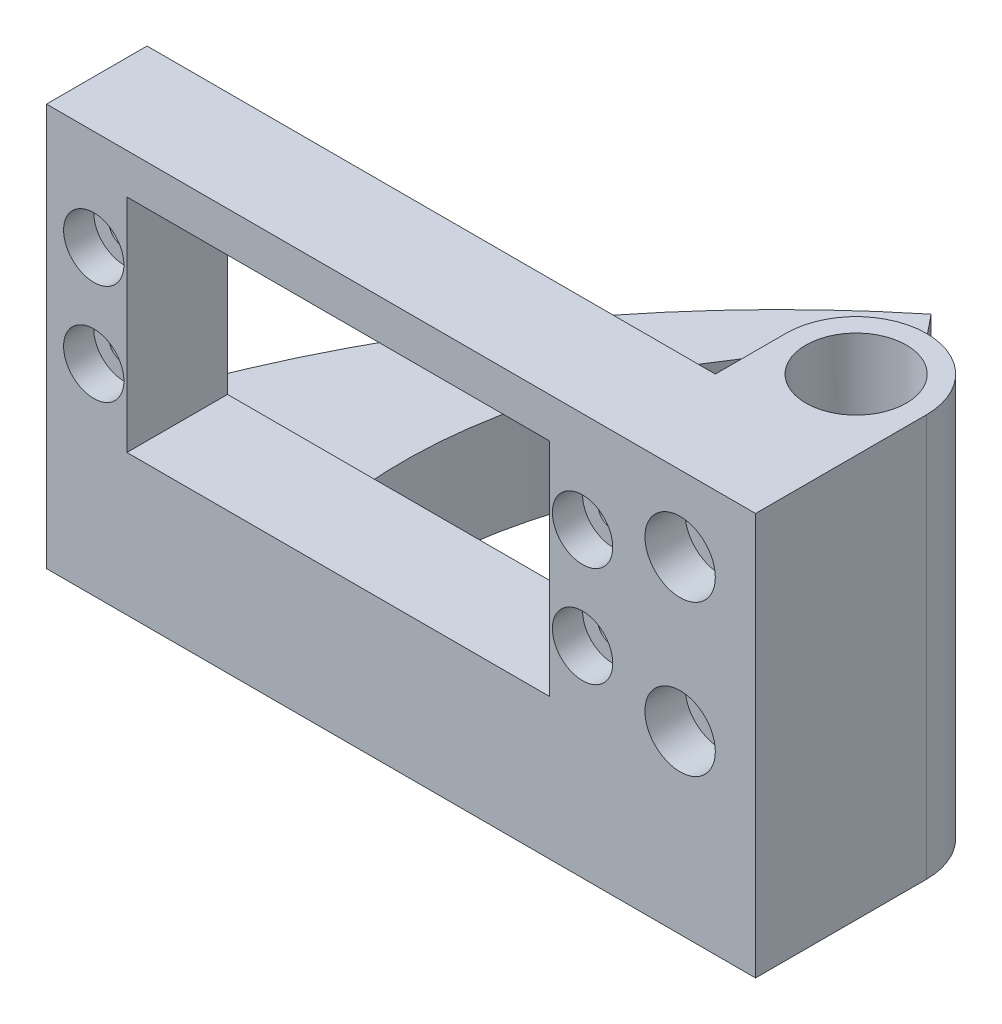
SolidWorks part; units mm, degrees
ref_plane "Front Plane" through (0, 0, 0) normal (0, 0, 1) x (1, 0, 0)
ref_plane "Top Plane" through (0, 0, 0) normal (0, 1, 0) x (1, 0, 0)
ref_plane "Right Plane" through (0, 0, 0) normal (1, 0, 0) x (0, 0, -1)
ref_axis "X" through (-88.99, 0, 0) along (1, 0, 0)
ref_axis "Y" through (0, 55, 0) along (0, -1, 0)
ref_axis "Z" through (0, 0, -88.99) along (0, 0, 1)
sketch "Sketch1" plane through (0, 0, 0) normal (0, 0, 1) x (1, 0, 0)
  line L0 (34, -7.5) -> (34, 7.5) construction
  line L1 (0, 0) -> (34, 0) construction
  line L2 (24.3, 5) -> (24.3, -5) construction
  line L3 (-21, 11) -> (21, 11)
  line L4 (-21, 11) -> (-21, -11)
  line L5 (-21, -11) -> (21, -11)
  line L6 (21, 11) -> (21, -11)
  line L7 (-21, 11) -> (21, -11) construction
  line L8 (-21, -11) -> (21, 11) construction
  line L9 (0, 0) -> (0, 11) construction
  line L10 (34, -15) -> (-29, -15)
  line L11 (-29, -15) -> (-29, 15)
  line L12 (-29, 15) -> (34, 15)
  line L13 (41.5, 7.5) -> (41.5, -7.5)
  line L14 (34, 0) -> (41.5, 0) construction
  line L15 (34, -15) -> (41.5, -15)
  line L16 (41.5, -15) -> (41.5, -7.5)
  line L17 (34, 15) -> (41.5, 15)
  line L18 (41.5, 15) -> (41.5, 7.5)
  circle A0 centre (34, -7.5) radius 3.5
  circle A1 centre (34, 7.5) radius 3.5
  circle A2 centre (24.3, 5) radius 1.5
  circle A3 centre (24.3, -5) radius 1.5
  circle A4 centre (-24.3, -5) radius 1.5
  circle A5 centre (-24.3, 5) radius 1.5
  arc A6 (34, 15) -> (41.5, 7.5) centre (34, 7.5) cw construction
  arc A7 (41.5, -7.5) -> (34, -15) centre (34, -7.5) cw construction
  point P14 (24.3, 0)
  dimension "D1" = 22
  dimension "D4" = 7
  dimension "D6" = 3
  dimension "D7" = 24.3
  dimension "D10" = 4
  dimension "D2" = 42
  dimension "D3" = 34
  dimension "D5" = 15
  dimension "D8" = 10
  dimension "D9" = 10
  dimension "D11" = 8
extrude "Boss-Extrude1" add sketch "Sketch1" along normal blind 10
sketch "Sketch2" plane through (0, 0, 0) normal (0, 0, 1) x (1, 0, 0)
  circle A0 centre (-24.3, 5) radius 3
  circle A1 centre (-24.3, -5) radius 3
  circle A2 centre (24.3, 5) radius 3
  circle A3 centre (24.3, -5) radius 3
  dimension "D1" = 6
extrude "Cut-Extrude1" cut sketch "Sketch2" against normal blind 3 from surface starting at face at (-25.8, -5, 10)
sketch "Sketch4" plane through (0, 0, 0) normal (0, 1, 0) x (1, 0, 0)
  line L0 (41.5, 0) -> (41.5, 7)
  line L1 (34, 0) -> (41.5, 0) construction
  line L2 (27.5, 7) -> (27.5, 0)
  line L3 (34, 0) -> (-29, 0) construction
  line L4 (0, 0) -> (34, 0) construction
  line L5 (41.5, 0) -> (27.5, 0)
  line L6 (-29, 0) -> (27.5, 0)
  line L7 (41.5, 0) -> (41.5, -10)
  line L8 (41.5, -10) -> (-29, -10)
  line L9 (-29, -10) -> (-29, 0)
  line L10 (3.0686, 45.8853) -> (6.2117, 41.9968)
  line L11 (3.0686, 45.8853) -> (6.9571, 49.0284) construction
  arc A0 (41.5, 7) -> (27.5, 7) centre (34.5, 7) ccw
  circle A1 centre (34.5, 7) radius 5
  arc A2 (41.5, 7) -> (27.5, 7) centre (34.5, 7) cw construction
  arc A3 (-9.9522, 0) -> (6.2117, 41.9968) centre (34.5, 7) cw
  arc A4 (3.0686, 45.8853) -> (-29, 0) centre (66.5114, -32.6028) ccw
  point P24 (41.5, -10)
  point P26 (41.5, -10)
  dimension "D1" = 10
  dimension "D2" = 2
  dimension "D3" = 45
  dimension "D4" = 5
  dimension "D6" = 5
  dimension "D5" = 60
extrude "Boss-Extrude2" add sketch "Sketch4" against normal blind 10 from surface contours L0 A0 L2 L5 A1 | L9 L8 L7 L5 L6 | L6 A3 L10 region at (34.5, 0, -0.198) region at (6.25, 0, 5) region at (-13.2311, 0, -18.1531) starting at face at (6.25, -15, 5)
extrude "Boss-Extrude3" add sketch "Sketch4<3>" along normal up to surface and the other way up to surface contours L0 A0 L2 L5 A1 region at (34.5, 0, -0.198) up to face at (6.25, 15, 5) other way up to face at (34.5, -15, -2)
sketch "Sketch4<3>" plane through (0, 0, 0) normal (0, 1, 0) x (1, 0, 0) same geometry as "Sketch4"
extrude "Boss-Extrude4" add sketch "Sketch1<3>" along normal offset from surface (6 mm away) 4 contours A1 | A0 region at (34, -7.5, 0) region at (34, 7.5, 0) up to face at (-21.3, -5, 10)
sketch "Sketch1<3>" plane through (0, 0, 0) normal (0, 0, 1) x (1, 0, 0) same geometry as "Sketch1"
